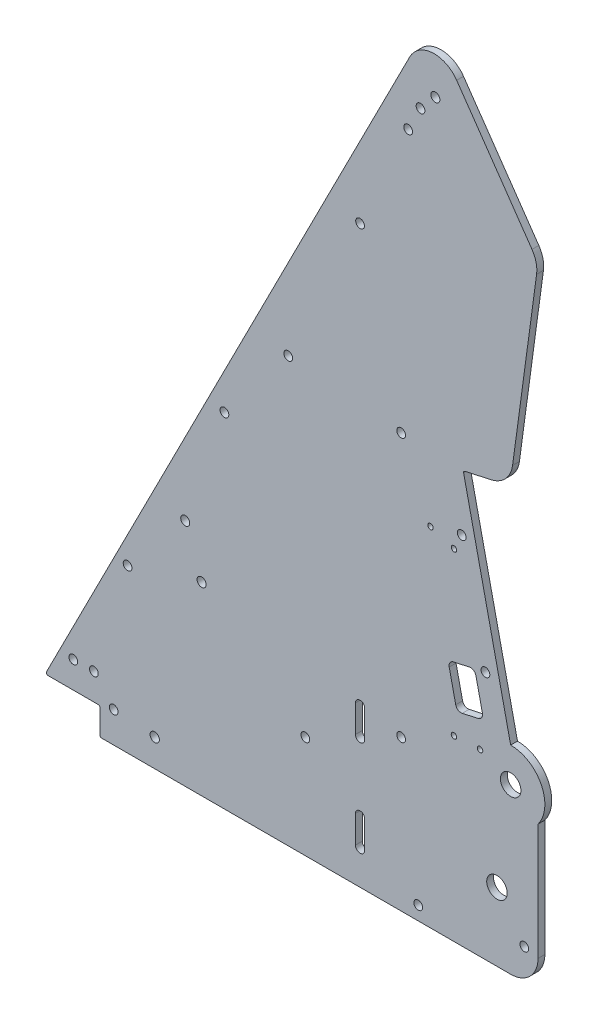
SolidWorks part; units mm, degrees
other "Markup1"
sketch "Sketch5"
ref_plane "Front Plane" through (0, 0, 0) normal (0, 0, 1) x (1, 0, 0)
ref_plane "Top Plane" through (0, 0, 0) normal (0, 1, 0) x (1, 0, 0)
ref_plane "Right Plane" through (0, 0, 0) normal (1, 0, 0) x (0, 0, -1)
sketch "Sketch1" plane through (0, 0, 0) normal (0, 0, 1) x (1, 0, 0)
  line L1 (228.6, -12.7) -> (228.6, 53.975)
  line L2 (178.7547, 351.4131) -> (0, 0)
  line L3 (228.6, 279.4) -> (178.7547, 351.4131)
  line L5 (0, 0) -> (25.4, 0)
  line L6 (25.4, 0) -> (25.4, -12.7)
  line L7 (25.4, -12.7) -> (228.6, -12.7)
  line L9 (215.9, 79.375) -> (193.9097, 178.5667)
  line L10 (193.9097, 178.5667) -> (215.6079, 183.377)
  line L11 (215.6079, 183.377) -> (228.6, 279.4)
  arc A0 (228.6, 53.975) -> (215.9, 79.375) centre (215.9, 63.5) ccw
  dimension "D7" = 12.7
  dimension "D8" = 76.2
  dimension "D10" = 31.75
  dimension "D2" = 292.1
  dimension "D3" = 25.4
  dimension "D4" = 215.9
  dimension "D5" = 394.2644
  dimension "D6" = 203.2
  dimension "D9" = 63.039
  dimension "D11" = 101.6
  dimension "D12" = 12.5
  dimension "D13" = 22.225
extrude "Boss-Extrude1" add sketch "Sketch1" along normal blind 3.175
sketch "Sketch2" plane through (0, 0, 3.175) normal (0, 0, 1) x (1, 0, 0)
  line L0 (178.7547, 351.4131) -> (0, 0) construction
  line L1 (25.4, -12.7) -> (228.6, -12.7) construction
  line L2 (215.9, 79.375) -> (193.9097, 178.5667) construction
  line L3 (193.9097, 178.5667) -> (215.6079, 183.377) construction
  line L4 (215.9, 79.375) -> (193.9097, 178.5667) construction
  line L5 (64.9432, 94.0578) -> (72.5445, 73.1732) construction
  line L6 (64.9432, 94.0578) -> (89.8317, 94.0578) construction
  line L10 (228.6, -12.7) -> (228.6, 53.975) construction
  circle A0 centre (64.9432, 94.0578) radius 2.0955
  circle A1 centre (180.975, 322.1643) radius 2.0955
  circle A2 centre (72.5445, 73.1732) radius 2.0955
  circle A3 centre (193.2078, 152.3944) radius 2.032
  circle A4 centre (215.9, 63.5) radius 4.7625
  circle A7 centre (173.0375, -6.35) radius 2.032
  circle A8 centre (204.203, 102.7985) radius 2.032
  circle A26 centre (209.55, 19.05) radius 4.7625
  arc A30 (228.6, 53.975) -> (215.9, 79.375) centre (215.9, 63.5) ccw construction
  circle A31 centre (165.1, 179.3875) radius 2.032
  dimension "D3" = 4.191
  dimension "D5" = 4.191
  dimension "D9" = 4.191
  dimension "D20" = 9.525
  dimension "D23" = 9.525
  dimension "D18" = 4.064
  dimension "D26" = 4.064
  dimension "D14" = 4.064
  dimension "D2" = 15.24
  dimension "D6" = 15.24
  dimension "D7" = 22.225
  dimension "D21" = 44.45
  dimension "D22" = 6.35
  dimension "D19" = 160.3375
  dimension "D24" = 44.45
  dimension "D25" = 6.35
  dimension "D27" = 25.4
  dimension "D28" = 50.8
  dimension "D29" = 6.35
  dimension "D17" = 6.35
  dimension "D33" = 55.5625
  dimension "D15" = 114.3
  dimension "D4" = 180.975
  dimension "D8" = 70
extrude "Cut-Extrude1" cut sketch "Sketch2" against normal through all
sketch "Sketch7" plane through (0, 0, 3.175) normal (0, 0, 1) x (1, 0, 0)
  line L0 (146.05, 3.175) -> (146.05, 15.875) construction
  line L1 (143.891, 3.175) -> (143.891, 15.875)
  line L2 (148.209, 3.175) -> (148.209, 15.875)
  line L3 (146.05, 47.625) -> (146.05, 60.325) construction
  line L4 (143.891, 47.625) -> (143.891, 60.325)
  line L5 (148.209, 47.625) -> (148.209, 60.325)
  line L6 (25.4, -12.7) -> (228.6, -12.7) construction
  line L12 (228.6, -12.7) -> (228.6, 53.975) construction
  line L13 (25.4, -12.7) -> (228.6, -12.7) construction
  arc A0 (143.891, 3.175) -> (148.209, 3.175) centre (146.05, 3.175) ccw
  arc A1 (148.209, 15.875) -> (143.891, 15.875) centre (146.05, 15.875) ccw
  arc A2 (143.891, 47.625) -> (148.209, 47.625) centre (146.05, 47.625) ccw
  arc A3 (148.209, 60.325) -> (143.891, 60.325) centre (146.05, 60.325) ccw
  circle A8 centre (50.8, 0) radius 2.159
  point P2 (146.05, 9.525)
  point P9 (146.05, 53.975)
  dimension "D1" = 4.318
  dimension "D5" = 4.318
  dimension "D2" = 12.7
  dimension "D3" = 12.7
  dimension "D4" = 44.45
  dimension "D6" = 95.25
  dimension "D7" = 82.55
  dimension "D8" = 15.875
  dimension "D9" = 12.7
extrude "Cut-Extrude2" cut sketch "Sketch7" against normal through all
sketch "Sketch10" plane through (0, 0, 3.175) normal (0, 0, 1) x (1, 0, 0)
  circle A1 centre (165.1, 57.15) radius 2.032
  circle A2 centre (120.65, 34.925) radius 2.032
  circle A3 centre (13.0465, 12.3347) radius 2.032
  circle A4 centre (22.5715, 12.3347) radius 2.032
  circle A5 centre (38.2114, 62.6398) radius 2.032
  dimension "D1" = 4.064
  dimension "D2" = 4.064
  dimension "D4" = 63.5
  dimension "D5" = 69.85
extrude "Cut-Extrude3" cut sketch "Sketch10" against normal up to next
fillet "Fillet1" radius 12.7 4 edges at (228.6, -12.7, 1.5875) (178.7547, 351.4131, 1.5875) (215.6079, 183.377, 1.5875) (228.6, 279.4, 1.5875)
fillet "Fillet2" radius 0.7937 4 edges at (25.4, -12.7, 1.5875) (25.4, 0, 1.5875) (193.9097, 178.5667, 1.5875) (0, 0, 1.5875)
sketch "Sketch12" plane through (0, 0, 3.175) normal (0, 0, 1) x (1, 0, 0)
  circle A0 centre (31.75, 1.5875) radius 2.032
  circle A1 centre (222.25, 1.5875) radius 2.032
  dimension "D1" = 4.064
extrude "Cut-Extrude5" cut sketch "Sketch12" against normal through all
sketch "Sketch13" plane through (0, 0, 3.175) normal (0, 0, 1) x (1, 0, 0)
  line L2 (194.6847, 178.7385) -> (207.144, 181.5006) construction
  line L5 (199.2434, 101.699) -> (189.6226, 145.0954) construction
  line L6 (189.6022, 69.9806) -> (201.7089, 70.5092) construction
  line L7 (186.8444, 98.9502) -> (199.2434, 101.699)
  line L8 (186.8444, 98.9502) -> (190.9676, 80.3518)
  line L9 (190.9676, 80.3518) -> (203.3665, 83.1006)
  line L10 (199.2434, 101.699) -> (203.3665, 83.1006)
  line L11 (189.6022, 69.9806) -> (190.9676, 80.3518) construction
  line L12 (201.7089, 70.5092) -> (203.3665, 83.1006) construction
  line L13 (215.9, 79.375) -> (194.0815, 177.7917) construction
  line L14 (178.7216, 148.5324) -> (189.6226, 145.0954) construction
  circle A0 centre (189.6022, 69.9806) radius 1.27
  circle A1 centre (201.7089, 70.5092) radius 1.27
  circle A2 centre (178.7216, 148.5324) radius 1.27
  circle A3 centre (189.6226, 145.0954) radius 1.27
  point P6 (178.5729, 149.0948)
  dimension "D7" = 2.54
  dimension "D2" = 11.43
  dimension "D3" = 76.2
  dimension "D4" = 12.7
  dimension "D5" = 19.05
  dimension "D6" = 120
  dimension "D8" = 110
  dimension "D9" = 80
  dimension "D10" = 12.7
  dimension "D11" = 44.45
  dimension "D12" = 11.43
extrude "Cut-Extrude6" cut sketch "Sketch13" against normal through all both and the other way through all
sketch "Sketch14" plane through (0, 0, 3.175) normal (0, 0, 1) x (1, 0, 0)
  line L0 (26.1937, -12.7) -> (215.9, -12.7) construction
  line L1 (228.6, 0) -> (228.6, 53.975) construction
  circle A0 centre (146.05, 254) radius 2.032
  circle A1 centre (112.7125, 184.15) radius 2.032
  dimension "D1" = 4.064
  dimension "D2" = 196.85
  dimension "D3" = 115.8875
  dimension "D4" = 82.55
  dimension "D5" = 266.7
extrude "Cut-Extrude7" cut sketch "Sketch14" against normal up to next
sketch "Sketch15" plane through (0, 0, 3.175) normal (0, 0, 1) x (1, 0, 0)
  line L0 (169.1053, 332.4434) -> (0.5868, 1.1536) construction
  circle A0 centre (83.1368, 146.6315) radius 2.032
  circle A1 centre (174.0995, 314.25) radius 2.032
  circle A2 centre (168.3414, 302.9303) radius 2.032
  circle A3 centre (174.0995, 314.25) radius 1.905 construction
  circle A4 centre (168.3414, 302.9303) radius 1.905 construction
  dimension "D1" = 4.064
  dimension "D4" = 4.064
  dimension "D2" = 7.62
  dimension "D3" = 82.55
extrude "Cut-Extrude8" cut sketch "Sketch15" against normal through all
fillet "Fillet3" radius 2.54 4 edges at (199.2434, 101.699, 1.5875) (186.8444, 98.9502, 1.5875) (190.9676, 80.3518, 1.5875) (203.3665, 83.1006, 1.5875)
equation "\"D6@Sketch2\"=\"D2@Sketch2\""
